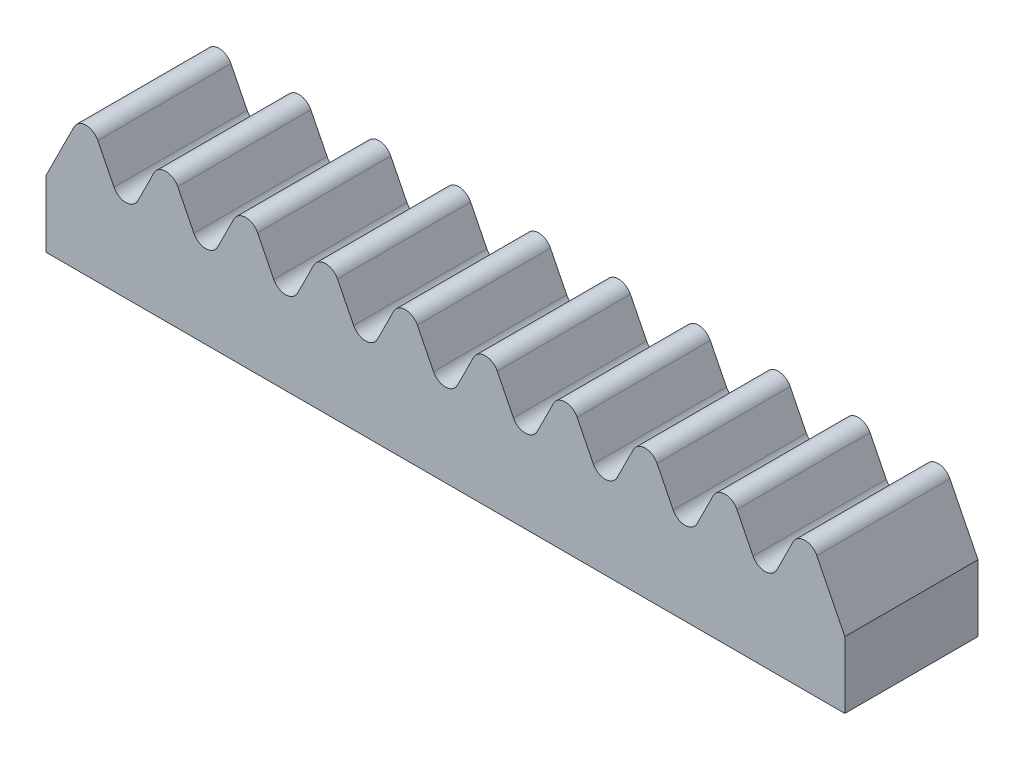
SolidWorks part; units mm, degrees
material "ABS"
ref_plane "Front Plane" through (0, 0, 0) normal (0, 0, 1) x (1, 0, 0)
ref_plane "Top Plane" through (0, 0, 0) normal (0, 1, 0) x (1, 0, 0)
ref_plane "Right Plane" through (0, 0, 0) normal (1, 0, 0) x (0, 0, -1)
sketch "Sketch2" plane through (0, 0, 0) normal (0, 0, 1) x (1, 0, 0)
  line L0 (-18, 0) -> (18, 0)
  line L2 (18, 0) -> (18, 2.5)
  line L11 (-11.5528, 3.3944) -> (-10.9472, 4.6056)
  line L12 (-9.4472, 3.3944) -> (-10.0528, 4.6056)
  line L13 (-8.5528, 3.3944) -> (-7.9472, 4.6056)
  line L14 (-6.4472, 3.3944) -> (-7.0528, 4.6056)
  line L15 (-5.5528, 3.3944) -> (-4.9472, 4.6056)
  line L16 (-3.4472, 3.3944) -> (-4.0528, 4.6056)
  line L17 (-2.5528, 3.3944) -> (-1.9472, 4.6056)
  line L18 (-0.4472, 3.3944) -> (-1.0528, 4.6056)
  line L19 (0.4472, 3.3944) -> (1.0528, 4.6056)
  line L20 (2.5528, 3.3944) -> (1.9472, 4.6056)
  line L21 (3.4472, 3.3944) -> (4.0528, 4.6056)
  line L22 (5.5528, 3.3944) -> (4.9472, 4.6056)
  line L23 (6.4472, 3.3944) -> (7.0528, 4.6056)
  line L24 (8.5528, 3.3944) -> (7.9472, 4.6056)
  line L25 (9.4472, 3.3944) -> (10.0528, 4.6056)
  line L26 (11.5528, 3.3944) -> (10.9472, 4.6056)
  line L27 (12.4472, 3.3944) -> (13.0528, 4.6056)
  line L28 (14.5528, 3.3944) -> (13.9472, 4.6056)
  line L29 (15.4472, 3.3944) -> (16.0528, 4.6056)
  line L30 (18, 2.5) -> (16.9472, 4.6056)
  line L31 (-11.5528, 3.3944) -> (-12, 2.5)
  line L32 (-12, 2.5) -> (-12, 0)
  arc A2 (-10.9472, 4.6056) -> (-10.0528, 4.6056) centre (-10.5, 4.382) cw
  arc A3 (-7.9472, 4.6056) -> (-7.0528, 4.6056) centre (-7.5, 4.382) cw
  arc A4 (-4.9472, 4.6056) -> (-4.0528, 4.6056) centre (-4.5, 4.382) cw
  arc A5 (-1.9472, 4.6056) -> (-1.0528, 4.6056) centre (-1.5, 4.382) cw
  arc A6 (1.0528, 4.6056) -> (1.9472, 4.6056) centre (1.5, 4.382) cw
  arc A7 (4.0528, 4.6056) -> (4.9472, 4.6056) centre (4.5, 4.382) cw
  arc A8 (7.0528, 4.6056) -> (7.9472, 4.6056) centre (7.5, 4.382) cw
  arc A9 (10.0528, 4.6056) -> (10.9472, 4.6056) centre (10.5, 4.382) cw
  arc A10 (13.0528, 4.6056) -> (13.9472, 4.6056) centre (13.5, 4.382) cw
  arc A11 (16.0528, 4.6056) -> (16.9472, 4.6056) centre (16.5, 4.382) cw
  arc A12 (14.5528, 3.3944) -> (15.4472, 3.3944) centre (15, 3.618) ccw
  arc A13 (11.5528, 3.3944) -> (12.4472, 3.3944) centre (12, 3.618) ccw
  arc A14 (8.5528, 3.3944) -> (9.4472, 3.3944) centre (9, 3.618) ccw
  arc A15 (5.5528, 3.3944) -> (6.4472, 3.3944) centre (6, 3.618) ccw
  arc A16 (2.5528, 3.3944) -> (3.4472, 3.3944) centre (3, 3.618) ccw
  arc A17 (-0.4472, 3.3944) -> (0.4472, 3.3944) centre (0, 3.618) ccw
  arc A18 (-3.4472, 3.3944) -> (-2.5528, 3.3944) centre (-3, 3.618) ccw
  arc A19 (-6.4472, 3.3944) -> (-5.5528, 3.3944) centre (-6, 3.618) ccw
  arc A20 (-9.4472, 3.3944) -> (-8.5528, 3.3944) centre (-9, 3.618) ccw
  point P4 (0, 0)
  dimension "D3" = 0.5
extrude "Boss-Extrude1" add sketch "Sketch2" along normal blind 5 contours A20 L12 A2 L11 L31 L32 L0 L2 L30 A11 L29 A12 L28 A10 L27 A13 L26 A9 L25 A14 L24 A8 L23 A15 L22 A7 L21 A16 L20 A6 L19 A17 L18 A5 L17 A18 L16 A4 L15 A19 L14 A3 L13 region at (3, 2.053, 0)
